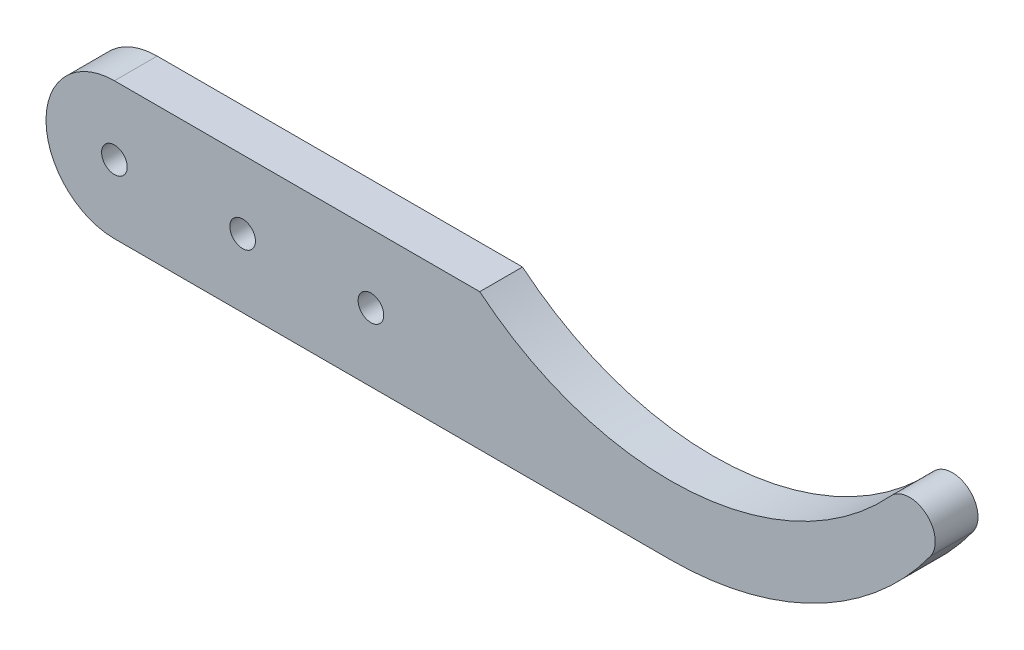
SolidWorks part; units mm, degrees
ref_plane "Plan de face" through (0, 0, 0) normal (0, 0, 1) x (1, 0, 0)
ref_plane "Plan de dessus" through (0, 0, 0) normal (0, 1, 0) x (1, 0, 0)
ref_plane "Plan de droite" through (0, 0, 0) normal (1, 0, 0) x (0, 0, -1)
sketch "Esquisse1" plane through (0, 0, 0) normal (0, 0, 1) x (1, 0, 0)
  line L0 (0, 0) -> (80, 0) construction
  line L1 (20, 0) -> (20, 23.8674) construction
  line L2 (0, 0) -> (0, 35) construction
  line L3 (0, 35) -> (50, 35) construction
  line L4 (0, 8) -> (20, 8)
  line L5 (75.7895, 11.3377) -> (78, 9.3095) construction
  line L6 (20, 8) -> (27.7289, 8)
  line L7 (0, -8) -> (50, -8)
  line L8 (50, 35) -> (50, -8) construction
  line L9 (0, 8) -> (-15, 8)
  line L10 (0, 0) -> (-15, 0) construction
  line L11 (0, -8) -> (-15, -8)
  circle A0 centre (0, 0) radius 1.5
  arc A1 (0, 8) -> (0, -8) centre (0, 0) ccw construction
  circle A2 centre (50, 35) radius 35 construction
  arc A3 (27.7289, 8) -> (75.7895, 11.3377) centre (50, 35) ccw
  arc A4 (75.7895, 11.3377) -> (80.4313, 7.5521) centre (78, 9.3095) cw
  arc A5 (50, -8) -> (80.4313, 7.5521) centre (50, 29.5491) ccw
  circle A6 centre (15, 0) radius 1.5
  arc A7 (-15, 8) -> (-15, -8) centre (-15, 0) ccw
  circle A8 centre (-15, 0) radius 1.5
  dimension "D3" = 3
  dimension "D4" = 35
  dimension "D6" = 70
  dimension "D7" = 3
  dimension "D8" = 8
  dimension "D9" = 28
  dimension "D10" = 15
  dimension "D11" = 8
  dimension "D1" = 20
  dimension "D2" = 80
  dimension "D5" = 50
  dimension "D12" = 15
extrude "Boss.-Extru.1" add sketch "Esquisse1" along normal blind 5
